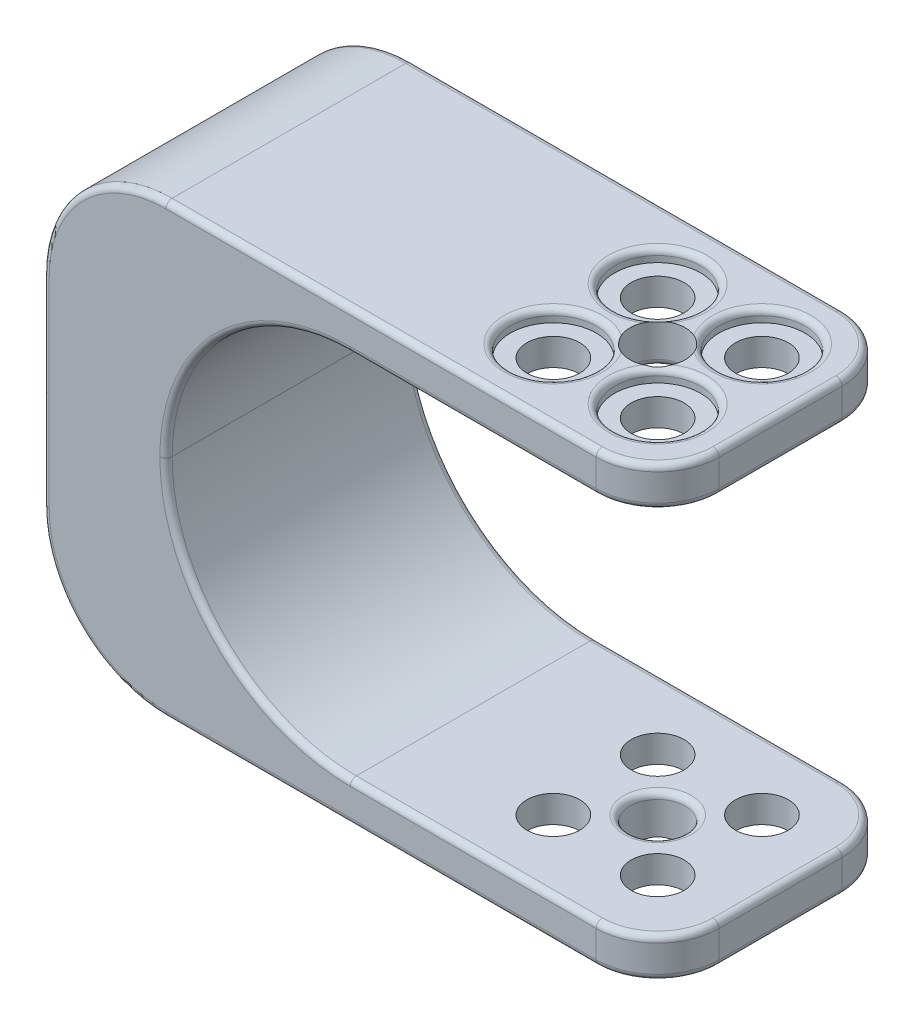
SolidWorks part; units mm, degrees
ref_plane "Front Plane" through (0, 0, 0) normal (0, 0, 1) x (1, 0, 0)
ref_plane "Top Plane" through (0, 0, 0) normal (0, 1, 0) x (1, 0, 0)
ref_plane "Right Plane" through (0, 0, 0) normal (1, 0, 0) x (0, 0, -1)
sketch "Sketch1" plane through (0, 0, 0) normal (0, 1, 0) x (1, 0, 0)
  line L0 (44.2288, -4.6089) -> (-5.7712, -4.6089) construction
  line L1 (-5.7712, 5.3911) -> (44.2288, 5.3911)
  line L2 (-5.7712, 5.3911) -> (-5.7712, -14.6089)
  line L3 (-5.7712, -14.6089) -> (44.2288, -14.6089)
  line L4 (44.2288, 5.3911) -> (44.2288, -14.6089)
  line L5 (34.2288, -4.6089) -> (43.1272, -13.5073) construction
  circle A0 centre (34.2288, -4.6089) radius 2.25
  circle A1 centre (38.4714, -8.8515) radius 2.15
  circle A2 centre (29.9862, -8.8515) radius 2.15
  circle A3 centre (29.9862, -0.3663) radius 2.15
  circle A4 centre (38.4714, -0.3663) radius 2.15
  point P20 (34.2288, -4.6089)
  dimension "D4" = 4.5
  dimension "D5" = 4.3
  dimension "D1" = 20
  dimension "D2" = 50
  dimension "D3" = 10
  dimension "D6" = 6
  dimension "D7" = 4
extrude "Boss-Extrude1" add sketch "Sketch1" along normal blind 36.4
sketch "Sketch2" plane through (0, 0, -5.3911) normal (0, 0, -1) x (-1, 0, 0)
  line L0 (-44.2288, 36.4) -> (-44.2288, 0) construction
  line L1 (-44.2288, 33.2) -> (-19.2188, 33.2)
  line L2 (-44.2288, 33.2) -> (-44.2288, 3.2)
  line L3 (-44.2288, 3.2) -> (-19.2188, 3.2)
  line L4 (-4.2288, 18.21) -> (-4.2288, 18.19)
  line L5 (5.7712, 36.4) -> (5.7712, 0) construction
  line L7 (-44.2288, 36.4) -> (-4.2288, 36.4)
  line L8 (-44.2288, 36.4) -> (-44.2288, 0)
  line L9 (-44.2288, 0) -> (-4.2288, 0)
  line L10 (5.7712, 26.4) -> (5.7712, 10)
  arc A0 (-4.2288, 18.19) -> (-19.2188, 3.2) centre (-19.2188, 18.19) cw
  arc A1 (-19.2188, 33.2) -> (-4.2288, 18.21) centre (-19.2188, 18.21) cw
  arc A2 (-4.2288, 0) -> (5.7712, 10) centre (-4.2288, 10) ccw
  arc A3 (-4.2288, 36.4) -> (5.7712, 26.4) centre (-4.2288, 26.4) cw
  point P8 (5.7712, 18.2)
  point P9 (-44.2288, 18.2)
  point P22 (5.7712, 0)
  line M1 (-44.2288, 0) -> (5.7712, 0)
  line M2 (5.7712, 0) -> (5.7712, 36.4)
  line M3 (5.7712, 36.4) -> (-44.2288, 36.4)
  line M4 (-44.2288, 36.4) -> (-44.2288, 0)
  dimension "D4" = 14.99
  dimension "D5" = 10
  dimension "D1" = 30
  dimension "D2" = 0
  dimension "D3" = 40
extrude "Cut-Extrude1" cut sketch "Sketch2" against normal blind 36.4 contours A1 L1 L3 A0 L4 M4 | A3 M3 M2 | A2 M1 M2 region at (25.684, 18.2, -5.3911) region at (-3.5375, 34.1663, -5.3911) region at (-3.5375, 2.2337, -5.3911)
sketch "Sketch4" plane through (0, 0, 0) normal (0, -1, 0) x (1, 0, 0)
  circle A0 centre (29.9862, 8.8515) radius 3.5
  circle A1 centre (38.4714, 8.8515) radius 3.5
  circle A2 centre (38.4714, 0.3663) radius 3.5
  circle A3 centre (29.9862, 0.3663) radius 3.5
  point P12 (34.2288, 4.6089)
  dimension "D1" = 7
  dimension "D2" = 4
extrude "Cut-Extrude2" cut sketch "Sketch4" against normal blind 1
fillet "Fillet1" radius 0.5 5 edges at (38.4714, 0, -3.1337) (29.9862, 0, -3.1337) (38.4714, 0, 5.3515) (29.9862, 0, 5.3515) (34.2288, 3.2, 2.3589)
fillet "Fillet2" radius 0.5 1 edges at (34.2288, 33.2, 2.3589)
sketch "Sketch6" plane through (0, 36.4, 0) normal (0, 1, 0) x (1, 0, 0)
  circle A0 centre (29.9862, -0.3663) radius 3.5
  circle A1 centre (38.4714, -0.3663) radius 3.5
  circle A2 centre (38.4714, -8.8515) radius 3.5
  circle A3 centre (29.9862, -8.8515) radius 3.5
  point P12 (34.2288, -4.6089)
  dimension "D1" = 7
  dimension "D2" = 4
extrude "Cut-Extrude3" cut sketch "Sketch6" against normal blind 1
fillet "Fillet3" radius 0.5 4 edges at (38.4714, 36.4, 3.8663) (38.4714, 36.4, 12.3515) (29.9862, 36.4, 12.3515) (29.9862, 36.4, 3.8663)
fillet "Fillet4" radius 5 4 edges at (44.2288, 1.6, -5.3911) (44.2288, 1.6, 14.6089) (44.2288, 34.8, 14.6089) (44.2288, 34.8, -5.3911)
fillet "Fillet5" radius 0.5 32 edges at (29.2238, 33.2, -5.3911) (42.7643, 33.2, -3.9266) (44.2288, 33.2, 4.6089) (42.7643, 33.2, 13.1444) (29.2238, 33.2, 14.6089) (8.6193, 28.8095, 14.6089) (4.2288, 18.2, 14.6089) (8.6193, 7.5905, 14.6089) (29.2238, 3.2, 14.6089) (42.7643, 3.2, 13.1444) (44.2288, 3.2, 4.6089) (42.7643, 3.2, -3.9266) (29.2238, 3.2, -5.3911) (8.6193, 7.5905, -5.3911) (4.2288, 18.2, -5.3911) (42.7643, 36.4, -3.9266) (44.2288, 36.4, 4.6089) (42.7643, 36.4, 13.1444) (21.7288, 36.4, 14.6089) (-2.8423, 33.4711, 14.6089) (-5.7712, 18.2, 14.6089) (-2.8423, 2.9289, 14.6089) (21.7288, 0, 14.6089) (42.7643, 0, 13.1444) (44.2288, 0, 4.6089) (42.7643, 0, -3.9266) (21.7288, 0, -5.3911) (-2.8423, 2.9289, -5.3911) (-5.7712, 18.2, -5.3911) (-2.8423, 33.4711, -5.3911) (8.6193, 28.8095, -5.3911) (21.7288, 36.4, -5.3911)
